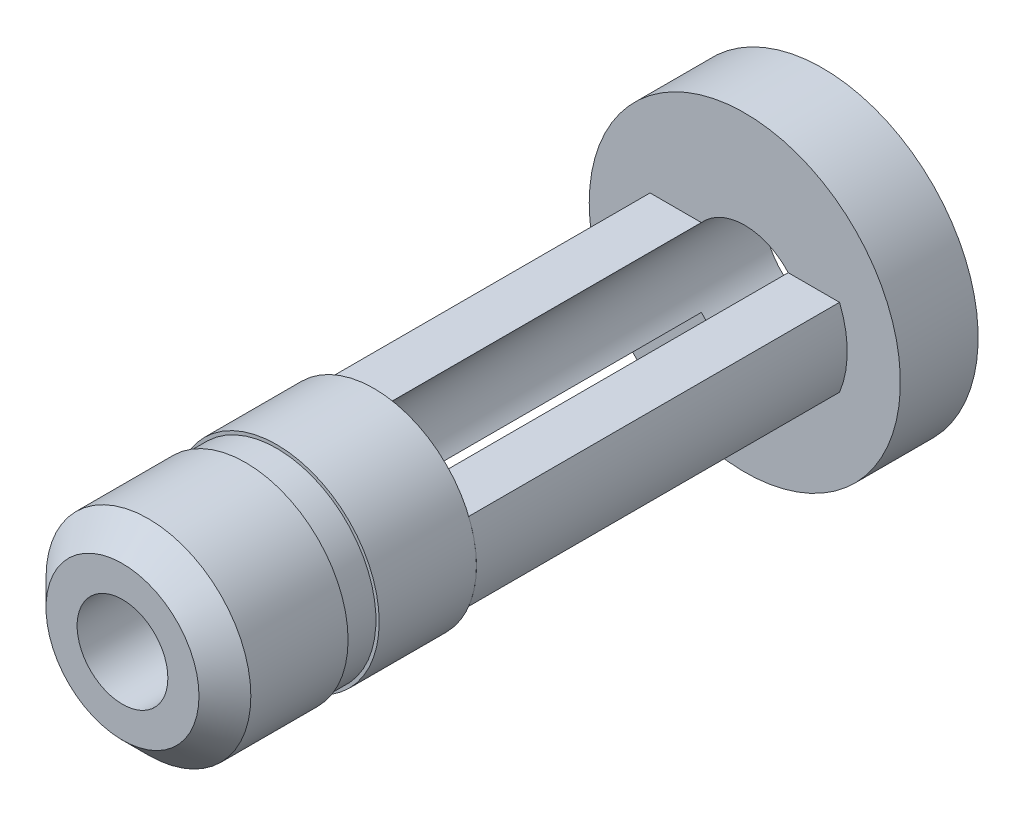
SolidWorks part; units mm, degrees
material "ASTM A36 Steel"
ref_plane "Front Plane" through (0, 0, 0) normal (0, 0, 1) x (1, 0, 0)
ref_plane "Top Plane" through (0, 0, 0) normal (0, 1, 0) x (1, 0, 0)
ref_plane "Right Plane" through (0, 0, 0) normal (1, 0, 0) x (0, 0, -1)
sketch "Sketch1" plane through (0, 0, 0) normal (0, 0, 1) x (1, 0, 0)
  circle A0 centre (0, 0) radius 7.9
  circle A1 centre (0, 0) radius 3.5
  dimension "D1" = 15.8
  dimension "D2" = 7
extrude "Boss-Extrude1" add sketch "Sketch1" along normal blind 19.4
chamfer "Chamfer1" distance 2 angle 45 1 edges at (7.9, 0, 19.4)
ref_plane "Plane7" [suppressed] through (0, 0, 7.5) normal (0, 0, -1) x (-1, 0, 0)
ref_plane "Plane8" through (0, 0, 9.9) normal (0, 0, -1) x (-1, 0, 0)
sketch "Sketch19" plane through (0, 0, 9.9) normal (0, 0, -1) x (-1, 0, 0)
  circle A0 centre (0, 0) radius 7.65
  circle A1 centre (0, 0) radius 7.9
  dimension "D1" = 15.3
extrude "Cut-Extrude6" cut sketch "Sketch19" along normal blind 2.4
sketch "Sketch20" plane through (0, 0, 0) normal (0, 0, -1) x (-1, 0, 0)
  circle A0 centre (0, 0) radius 7.9
  circle A1 centre (0, 0) radius 4.5
  dimension "D1" = 9
extrude "Boss-Extrude3" add sketch "Sketch20" along normal blind 28.6 separate body
sketch "Sketch21" plane through (0, 0, -28.6) normal (0, 0, -1) x (-1, 0, 0)
  line L1 (0, 3.0042) -> (-7.3065, 3.0042)
  line L9 (-7.3081, -3.0004) -> (0, -3.0004)
  line L12 (0, -3.0004) -> (7.3081, -3.0004)
  line L13 (0, 3.0042) -> (7.3065, 3.0042)
  circle A0 centre (0, 0) radius 7.9 construction
  arc A1 (-7.3065, 3.0042) -> (7.3065, 3.0042) centre (0, 0) cw
  arc A2 (-7.3081, -3.0004) -> (7.3081, -3.0004) centre (0, 0) ccw
extrude "Cut-Extrude7" cut sketch "Sketch21" against normal blind 28.6
ref_plane "Plane9" through (0, 0, -28.6) normal (0, 0, -1) x (-1, 0, 0)
sketch "Sketch22" plane through (0, 0, -28.6) normal (0, 0, -1) x (-1, 0, 0)
  circle A0 centre (0, 0) radius 12
  dimension "D1" = 24
extrude "Boss-Extrude4" add sketch "Sketch22" along normal blind 6
sketch "Sketch23" plane through (0, 0, -34.6) normal (0, 0, -1) x (-1, 0, 0)
  circle A0 centre (0, 0) radius 4.5
  dimension "D1" = 9
extrude "Cut-Extrude8" cut sketch "Sketch23" against normal up to next (6 mm away)
